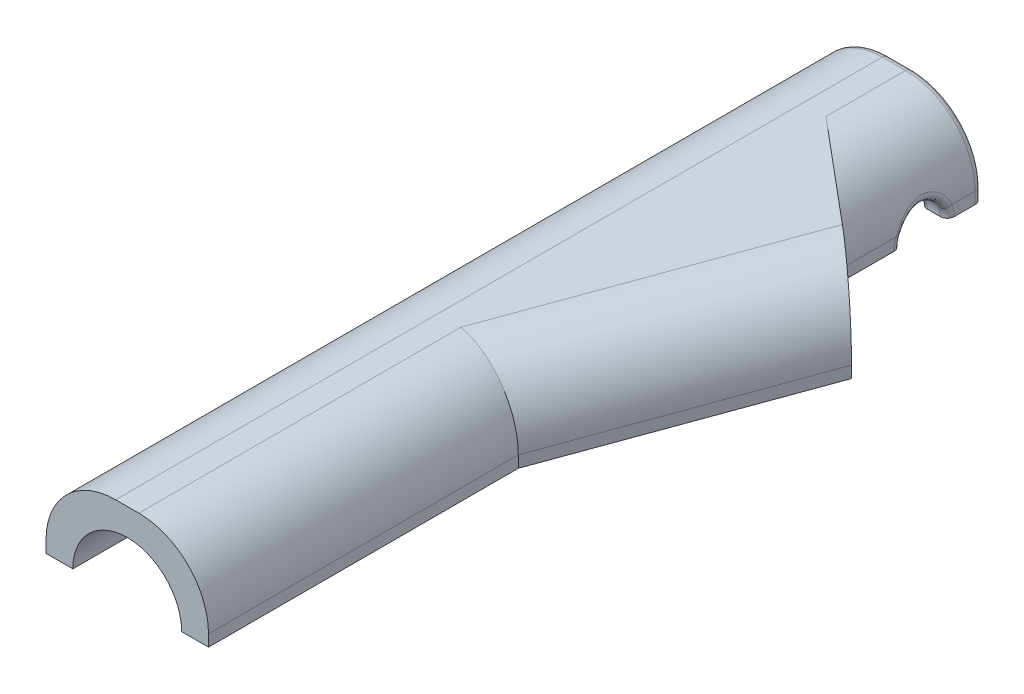
SolidWorks part; units mm, degrees
ref_plane "Front Plane" through (0, 0, 0) normal (0, 0, 1) x (1, 0, 0)
ref_plane "Top Plane" through (0, 0, 0) normal (0, 1, 0) x (1, 0, 0)
ref_plane "Right Plane" through (0, 0, 0) normal (1, 0, 0) x (0, 0, -1)
sketch "Sketch1" plane through (0, 0, 0) normal (0, 1, 0) x (1, 0, 0)
  line L0 (3.5, 10.4197) -> (7.3302, 7.2058)
  line L1 (-3.5, 16.6615) -> (3.5, 16.6615)
  line L2 (-3.5, 16.6615) -> (-3.5, -16.6615)
  line L3 (-3.5, -16.6615) -> (3.5, -16.6615)
  line L4 (3.5, 16.6615) -> (3.5, 10.4197)
  line L5 (-3.5, 16.6615) -> (3.5, -16.6615) construction
  line L6 (-3.5, -16.6615) -> (3.5, 16.6615) construction
  line L7 (7.3302, 7.2058) -> (3.5, -3.3177)
  line L9 (3.5, -3.3177) -> (3.5, -16.6615)
  point P0 (0, 0)
  dimension "D1" = 7
  dimension "D2" = 110
  dimension "D3" = 5
  dimension "D4" = 20
extrude "Boss-Extrude1" add sketch "Sketch1" along normal blind 3.5 contours L2 L3 L9 L7 L0 L4 L1
sketch "Sketch2" plane through (0, 0, 16.6615) normal (0, 0, 1) x (1, 0, 0)
  line L0 (-3.5, 0) -> (3.5, 0) construction
  line L1 (2.3437, 0) -> (-2.3437, 0)
  arc A0 (2.3437, 0) -> (-2.3437, 0) centre (0, 0) ccw
extrude "Cut-Extrude1" cut sketch "Sketch2" against normal through all
ref_plane "Plane1" through (3.7583, 0, -10.3257) normal (-0.342, 0, 0.9397) x (0, -1, 0)
sketch "Sketch3" plane through (3.7583, 0, -10.3257) normal (-0.342, 0, 0.9397) x (0, -1, 0)
  line L0 (0, 3.7252) -> (0, 1.7252)
  line L1 (0, -0.2748) -> (0, 4.4236) construction
  arc A0 (0, 3.7252) -> (0, 1.7252) centre (335.2485, 2.7252) ccw
  arc A1 (0, 1.7252) -> (0, 3.7252) centre (0, 2.7252) cw
  dimension "D1" = 2
  dimension "D2" = 2
extrude "Cut-Extrude2" cut sketch "Sketch3" along normal blind 15 contours A1 A0
fillet "Fillet1" radius 3 4 edges at (3.5, 3.5, 9.9896) (5.4151, 3.5, -1.944) (3.5, 3.5, -13.5406) (-3.5, 3.5, 0)
sketch "Sketch4" plane through (3.5, 0, 0) normal (1, 0, 0) x (0, 0, -1)
  line L0 (16.6615, 0) -> (10.4197, 0) construction
  line L1 (15.1615, 0) -> (13.1615, 0)
  arc A0 (13.1615, 0) -> (15.1615, 0) centre (14.1615, 0) cw
  dimension "D1" = 2
  dimension "D2" = 1.5
extrude "Cut-Extrude3" cut sketch "Sketch4" against normal blind 2
fillet "Fillet2" radius 0.3 3 edges at (3.5, 0.2588, -15.1274) (3.5, 0.2588, -13.1956) (3.4582, 0.9992, -14.2008)
fillet "Fillet3" radius 0.3 1 edges at (2.1211, 0.997, -14.0846)
fillet "Fillet4" radius 0.3 1 edges at (2.1211, 0.9969, 2.3711)
fillet "Fillet5" radius 0.3 5 edges at (-3.5, 0.25, -16.6615) (-2.6213, 2.6213, -16.6615) (0, 3.5, -16.6615) (3.5, 0.25, -16.6615) (2.6213, 2.6213, -16.6615)
